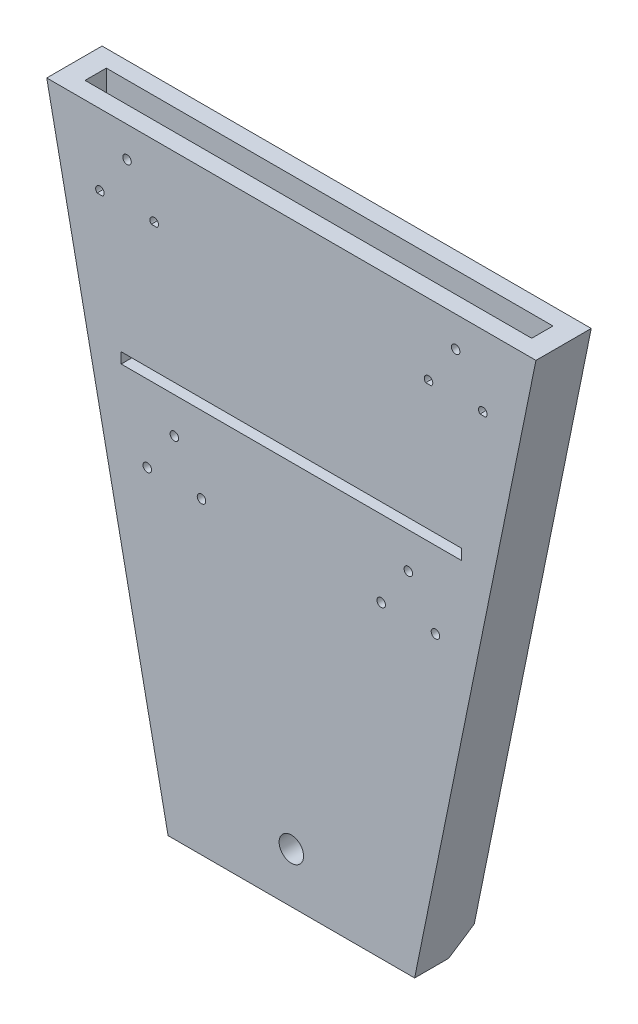
SolidWorks part; units mm, degrees
ref_plane "前视基准面" through (0, 0, 0) normal (0, 0, 1) x (1, 0, 0)
ref_plane "上视基准面" through (0, 0, 0) normal (0, 1, 0) x (1, 0, 0)
ref_plane "右视基准面" through (0, 0, 0) normal (1, 0, 0) x (0, 0, -1)
other "Configuration Table"
sketch "草图1" plane through (0, 0, 0) normal (0, 0, 1) x (1, 0, 0)
  line L0 (-60, 0) -> (60, 0)
  line L1 (0, 77.3448) -> (0, -71.5734) construction
  line L2 (-115, 270) -> (115, 270)
  line L3 (-115, 270) -> (-60, 0)
  line L4 (115, 270) -> (60, 0)
  point P3 (0, 0)
  point P8 (0, 270)
  dimension "D1" = 120
  dimension "D2" = 230
  dimension "D3" = 270
extrude "凸台-拉伸1" add sketch "草图1" along normal blind 8
sketch "草图2" plane through (0, 0, 8) normal (0, 0, 1) x (1, 0, 0)
  line L0 (-60, 0) -> (60, 0) construction
  line L1 (0, -1000) -> (0, 0.3) construction
  line L2 (0, 26.71) -> (0, 57.7278) construction
  line L3 (0.005, 0.31) -> (0, 0.3)
  line L4 (0, 26.71) -> (12.1089, 26.71)
  line L6 (0, 0.3) -> (17.4887, 0.3)
  line L7 (12.1089, 26.71) -> (17.4887, 0.3)
  line L8 (-115, 270) -> (-60, 0) construction
  arc A0 (0, 26.71) -> (0.005, 0.31) centre (0, 13.51) ccw
  dimension "D1" = 26.4
  dimension "D2" = 13.51
  dimension "D3" = 14.5
  dimension "D5" = 13.21
extrude "切除-拉伸1" cut sketch "草图2" against normal blind 8.9
sketch "草图3" plane through (0, 0, 8) normal (0, 0, 1) x (1, 0, 0)
  line L0 (-94.3261, 168.51) -> (94.3261, 168.51)
  line L1 (-115, 270) -> (-60, 0) construction
  line L2 (60, 0) -> (115, 270) construction
  line L4 (-96.3631, 178.51) -> (96.3631, 178.51)
  line L5 (-107.8704, 235) -> (107.8704, 235)
  point P0 (-115, 270)
  point P14 (0, 178.51)
  point P15 (0, 13.51)
  dimension "D1" = 155
  dimension "D2" = 10
  dimension "D3" = 35
sketch "草图5" plane through (0, 0, 0) normal (0, 0, -1) x (-1, 0, 0)
  line L4 (60, 0) -> (115, 270)
  line L5 (115, 270) -> (-115, 270)
  line L6 (-115, 270) -> (-60, 0)
  line L7 (-60, 0) -> (60, 0)
  line L8 (60, 0) -> (115, 270)
  line L9 (115, 270) -> (-115, 270)
  line L10 (-115, 270) -> (-60, 0)
  line L11 (-60, 0) -> (60, 0)
  dimension "D1" = 0
extrude "凸台-拉伸2" add sketch "草图5" along normal blind 8
sketch "草图6" plane through (0, 0, 8) normal (0, 0, 1) x (1, 0, 0)
  line L4 (-115, 270) -> (-60, 0)
  line L5 (-60, 0) -> (60, 0)
  line L6 (60, 0) -> (115, 270)
  line L7 (115, 270) -> (-115, 270)
  line L8 (-115, 270) -> (-60, 0)
  line L9 (-60, 0) -> (60, 0)
  line L10 (60, 0) -> (115, 270)
  line L11 (115, 270) -> (-115, 270)
  point P2 (0, 13.51)
  dimension "D1" = 0
extrude "凸台-拉伸3" add sketch "草图6" along normal blind 10
sketch "草图7" plane through (0, 0, 18) normal (0, 0, 1) x (1, 0, 0)
  circle A0 centre (0, 13.51) radius 5.75
  dimension "D1" = 11.5
extrude "切除-拉伸2" cut sketch "草图7" against normal blind 22
ref_plane "基准面1" through (0, 0, 18) normal (0, 0, 1) x (1, 0, 0)
sketch "草图9" plane through (0, 0, 18) normal (0, 0, 1) x (1, 0, 0)
  line L0 (-60, 0) -> (60, 0)
  line L1 (60, 0) -> (57.963, -10)
  line L2 (57.963, -10) -> (-57.963, -10)
  line L3 (-57.963, -10) -> (-60, 0)
  line L4 (60, 0) -> (115, 270) construction
  line L5 (-115, 270) -> (-60, 0) construction
  line L6 (60, 0) -> (115, 270)
  line L7 (-115, 270) -> (-60, 0)
  dimension "D1" = 10
extrude "凸台-拉伸5" add sketch "草图9" against normal blind 26 contours L3 L2 L1 L0 region at (0, -4.9712, 18)
ref_plane "基准面2" through (0, 0, -8) normal (0, 0, 1) x (1, 0, 0)
sketch "草图11" plane through (0, 0, -8) normal (0, 0, 1) x (1, 0, 0)
  line L0 (110.9179, 270) -> (53.8808, -10)
  line L1 (-110.9179, 270) -> (-53.8808, -10)
  line L2 (109.6932, 270) -> (52.6562, -10)
  line L3 (-109.6932, 270) -> (-52.6562, -10)
  line L4 (115, 270) -> (-115, 270)
  line L5 (-115, 270) -> (-57.963, -10)
  line L6 (-57.963, -10) -> (57.963, -10)
  line L7 (57.963, -10) -> (115, 270)
  line L8 (115, 270) -> (-115, 270)
  line L9 (-115, 270) -> (-57.963, -10)
  line L10 (-57.963, -10) -> (57.963, -10)
  line L11 (57.963, -10) -> (115, 270)
  dimension "D2" = 4
  dimension "D3" = 4
  dimension "D4" = 1.2
  dimension "D5" = 1.2
  dimension "D1" = 0
sketch "草图12" plane through (0, 0, -8) normal (0, 0, 1) x (1, 0, 0)
  line L0 (-115, 270) -> (-60, 0) construction
  line L1 (60, 0) -> (115, 270) construction
  line L2 (-115, 270) -> (-60, 0)
  line L3 (60, 0) -> (115, 270)
  line L4 (60, 0) -> (-60, 0)
  line L5 (57.963, -10) -> (60, 0)
  line L6 (-57.963, -10) -> (57.963, -10)
  line L7 (-60, 0) -> (-57.963, -10)
  line L8 (60, 0) -> (-60, 0)
  line L9 (57.963, -10) -> (60, 0)
  line L10 (-57.963, -10) -> (57.963, -10)
  line L11 (-60, 0) -> (-57.963, -10)
  line L12 (-109.6932, 270) -> (-52.6562, -10) construction
  line L13 (109.6932, 270) -> (52.6562, -10) construction
  line L14 (-110.9179, 270) -> (-53.8808, -10) construction
  line L15 (110.9179, 270) -> (53.8808, -10) construction
  line L16 (115, 270) -> (-115, 270)
  line L17 (-115, 270) -> (-57.963, -10)
  line L18 (-57.963, -10) -> (57.963, -10)
  line L19 (57.963, -10) -> (115, 270)
  line L20 (115, 270) -> (-115, 270)
  line L21 (-115, 270) -> (-57.963, -10)
  line L22 (-57.963, -10) -> (57.963, -10)
  line L23 (57.963, -10) -> (115, 270)
  line L24 (-109.6932, 270) -> (-52.6562, -10)
  line L25 (109.6932, 270) -> (52.6562, -10)
  line L26 (-110.9179, 270) -> (-53.8808, -10)
  line L27 (110.9179, 270) -> (53.8808, -10)
  dimension "D1" = 0
  dimension "D2" = 0
extrude "切除-拉伸4" cut sketch "草图12" along normal blind 21 contours L25 L8 L24 L22 region at (0, -4.9684, -8)
chamfer "倒角6" distance 5 angle 45 1 edges at (0, 0, -8)
chamfer "倒角8" distance 10 angle 45 2 edges at (-55.3096, -10, -8) (55.3096, -10, -8)
sketch "草图13" plane through (0, 270, 0) normal (0, 1, 0) x (1, 0, 0)
  line L1 (-105, 0) -> (105, 0)
  line L2 (-105, 0) -> (-105, -10)
  line L3 (-105, -10) -> (105, -10)
  line L4 (105, 0) -> (105, -10)
  line L5 (-105, 0) -> (105, -10) construction
  line L6 (-105, -10) -> (105, 0) construction
  line L7 (115, -18) -> (-115, -18) construction
  line L9 (-115, -18) -> (-115, 8) construction
  point P4 (0, -5)
  dimension "D1" = 210
  dimension "D2" = 10
  dimension "D3" = 13
  dimension "D4" = 115
extrude "切除-拉伸5" cut sketch "草图13" against normal blind 15
sketch "草图14" plane through (0, 0, 18) normal (0, 0, 1) x (1, 0, 0)
  line L0 (-96.3631, 178.51) -> (96.3631, 178.51) construction
  line L1 (-96.3631, 178.51) -> (96.3631, 178.51)
  line L2 (-94.3261, 168.51) -> (94.3261, 168.51) construction
  line L3 (-107.8704, 235) -> (107.8704, 235) construction
  line L4 (115, 270) -> (-115, 270)
  line L5 (-115, 270) -> (-57.963, -10)
  line L6 (-57.963, -10) -> (57.963, -10)
  line L7 (57.963, -10) -> (115, 270)
  line L8 (115, 270) -> (-115, 270)
  line L9 (-115, 270) -> (-57.963, -10)
  line L10 (-57.963, -10) -> (57.963, -10)
  line L11 (57.963, -10) -> (115, 270)
  line L12 (-94.3261, 168.51) -> (94.3261, 168.51)
  line L13 (-107.8704, 235) -> (107.8704, 235)
  line L14 (0, 270) -> (0, -10) construction
  line L15 (-80, 176.01) -> (80, 176.01)
  line L16 (-80, 176.01) -> (-80, 171.01)
  line L17 (-80, 171.01) -> (80, 171.01)
  line L18 (80, 176.01) -> (80, 171.01)
  line L19 (-80, 176.01) -> (80, 171.01) construction
  line L20 (-80, 171.01) -> (80, 176.01) construction
  point P14 (0, 173.51)
  dimension "D2" = 160
  dimension "D3" = 5
  dimension "D4" = 5
  dimension "D1" = 0
extrude "切除-拉伸6" cut sketch "草图14" against normal blind 10 contours L18 L15 L16 L17 region at (0, 173.51, 18)
sketch "草图16" plane through (0, 0, 18) normal (0, 0, 1) x (1, 0, 0)
  line L0 (0, 270) -> (0, -27.9065) construction
  line L2 (115, 270) -> (-115, 270) construction
  line L3 (-107.8704, 235) -> (107.8704, 235) construction
  line L4 (-94.3261, 168.51) -> (94.3261, 168.51) construction
  line L5 (-96.3631, 178.51) -> (96.3631, 178.51) construction
  line L6 (115, 270) -> (-115, 270)
  line L7 (-107.8704, 235) -> (107.8704, 235)
  line L8 (-94.3261, 168.51) -> (94.3261, 168.51)
  line L9 (-96.3631, 178.51) -> (96.3631, 178.51)
  line L11 (-90.2182, 178.51) -> (90.2182, 178.51)
  line L12 (-90.2182, 178.51) -> (-90.2182, 168.51)
  line L13 (-90.2182, 168.51) -> (90.2182, 168.51)
  line L14 (90.2182, 178.51) -> (90.2182, 168.51)
  line L15 (-90.2182, 178.51) -> (90.2182, 168.51) construction
  line L16 (-90.2182, 168.51) -> (90.2182, 178.51) construction
  circle A0 centre (-77.25, 255.6426) radius 2
  circle A1 centre (-90, 236.5) radius 2
  circle A2 centre (-64.5, 236.5) radius 2
  circle A3 centre (64.5, 236.5) radius 2
  circle A4 centre (90, 236.5) radius 2
  circle A5 centre (77.25, 255.6426) radius 2
  circle A6 centre (-55, 154.1526) radius 2
  circle A7 centre (-67.75, 135.01) radius 2
  circle A8 centre (-42.25, 135.01) radius 2
  circle A9 centre (42.25, 135.01) radius 2
  circle A10 centre (67.75, 135.01) radius 2
  circle A11 centre (55, 154.1526) radius 2
  point P15 (0, 173.51)
  dimension "D6" = 4
  dimension "D7" = 4
  dimension "D8" = 4
  dimension "D15" = 4
  dimension "D16" = 4
  dimension "D17" = 4
  dimension "D1" = 33.5
  dimension "D2" = 33.5
  dimension "D3" = 25.5
  dimension "D4" = 23
  dimension "D5" = 23
  dimension "D9" = 90
  dimension "D10" = 23
  dimension "D11" = 23
  dimension "D12" = 25.5
  dimension "D13" = 33.5
  dimension "D14" = 33.5
  dimension "D18" = 55
extrude "切除-拉伸7" cut sketch "草图16" against normal blind 10 contours A0 | A1 | A2 | A5 | A3 | A4 | A6 | A8 | A11 | A9 | A10 | A7 region at (-90, 236.6324, 18) region at (90, 236.6324, 18) region at (64.5, 236.6324, 18) region at (-64.5, 236.6324, 18) region at (-77.25, 255.6426, 18) region at (77.25, 255.6426, 18) region at (-55, 154.1526, 18) region at (-42.25, 135.01, 18) region at (42.25, 135.01, 18) region at (67.75, 135.01, 18) region at (55, 154.1526, 18)
sketch "草图17" plane through (0, 0, 18) normal (0, 0, 1) x (1, 0, 0)
  point P0 (-60.2489, 215.8027)
  point P2 (-96.3631, 178.51)
sketch "草图18" plane through (0, 0, 0) normal (0, -1, 0) x (1, 0, 0)
  line L4 (-54.6932, 13) -> (-54.6932, -3)
  line L5 (-54.6932, -3) -> (54.6932, -3)
  line L6 (54.6932, -3) -> (54.6932, 13)
  line L7 (54.6932, 13) -> (-54.6932, 13)
  line L8 (-54.6932, 13) -> (-54.6932, -3)
  line L10 (54.6932, -3) -> (54.6932, 13)
  line L11 (54.6932, 13) -> (-54.6932, 13)
  line L13 (-54.6932, -3) -> (54.6932, -3)
  dimension "D1" = 0
extrude "凸台-拉伸7" add sketch "草图18" along normal blind 2
chamfer "倒角10" distance 2 angle 45 1 edges at (0, -2, -3)
